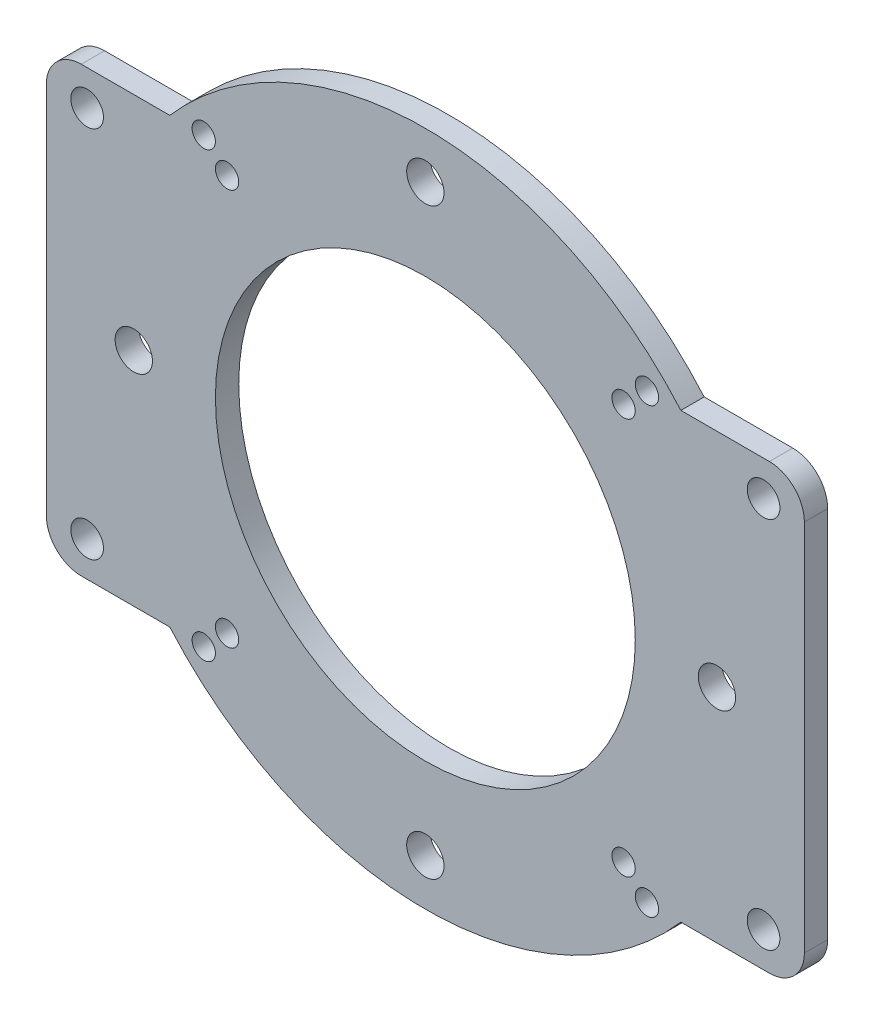
SolidWorks part; units mm, degrees
ref_plane "Front Plane" through (0, 0, 0) normal (0, 0, 1) x (1, 0, 0)
ref_plane "Top Plane" through (0, 0, 0) normal (0, 1, 0) x (1, 0, 0)
ref_plane "Right Plane" through (0, 0, 0) normal (1, 0, 0) x (0, 0, -1)
sketch "Sketch1" plane through (0, 0, 0) normal (0, 0, 1) x (1, 0, 0)
  line L0 (-32.5, 19) -> (-21.9089, 19)
  line L1 (32.5, 19) -> (32.5, -19)
  line L2 (32.5, -19) -> (21.9089, -19)
  line L3 (-32.5, -19) -> (-32.5, 19)
  line L4 (0, 39) -> (0, -40.7055) construction
  line L5 (-43.0364, 0) -> (51.1093, 0) construction
  line L6 (21.9089, 19) -> (32.5, 19)
  line L7 (-21.9089, -19) -> (-32.5, -19)
  arc A0 (-21.9089, -19) -> (21.9089, -19) centre (0, 0) ccw
  arc A1 (21.9089, 19) -> (-21.9089, 19) centre (0, 0) ccw
  circle A2 centre (0, 0) radius 18
  point P12 (27.2045, 19)
  dimension "D1" = 58
  dimension "D4" = 36
  dimension "D2" = 65
  dimension "D3" = 38
extrude "Boss-Extrude1" add sketch "Sketch1" along normal blind 2
sketch "Sketch2" plane through (0, 0, 2) normal (0, 0, 1) x (1, 0, 0)
  line L0 (-33.5817, 0) -> (33.9726, 0) construction
  line L1 (0, 32.4479) -> (0, -34.6372) construction
  circle A0 centre (-29, 16) radius 1.4
  circle A1 centre (-29, -16) radius 1.4
  circle A2 centre (29, -16) radius 1.4
  circle A3 centre (29, 16) radius 1.4
  dimension "D1" = 2.8
  dimension "D2" = 58
  dimension "D3" = 32
extrude "Cut-Extrude1" cut sketch "Sketch2" against normal blind 2
sketch "Sketch3" plane through (0, 0, 2) normal (0, 0, 1) x (1, 0, 0)
  line L0 (0, 15.6309) -> (0, -13.6849) construction
  line L1 (-12.5553, 0) -> (11.836, 0) construction
  point P5 (-17, 17)
  point P6 (17, 17)
  point P7 (17, -17)
  point P8 (-17, -17)
  point P9 (19, 19)
  point P10 (19, -19)
  point P11 (-19, -19)
  point P12 (0, 0)
  point P13 (-19, 19)
  point P14 (19, 19.7089)
  point P15 (0, 0)
  point P16 (0, 0)
  point P17 (0, 0)
  dimension "D1" = 34
  dimension "D2" = 34
  dimension "D3" = 38
  dimension "D4" = 38
hole_wizard "Ø2.0mm Dowel Hole1" positions "3DSketch1" profile "Sketch4" hole size "Ø2.0" standard "ANSI Metric" end condition through all
sketch3d "3DSketch1"
  point P0 (-19, 19, 2)
  point P3 (-17, 17, 2)
  point P6 (17, 17, 2)
  point P9 (19, 19, 2)
  point P12 (17, -17, 2)
  point P15 (19, -19, 2)
  point P18 (-19, -19, 2)
  point P21 (-17, -17, 2)
sketch "Sketch4" plane through (-19, 19, 2) normal (1, 0, 0) x (0, -1, 0)
  line L0 (0, 0) -> (0, 2)
  line L1 (0, 2) -> (1, 2)
  line L2 (1, 2) -> (1, 0)
  line L5 (1, 0) -> (0, 0)
  line L11 (0, -6.35) -> (0, 107.95) construction
  dimension "Thru Hole Dia." = 2
  dimension "Thru Hole Depth" = 2
sketch "Sketch5" plane through (0, 0, 0) normal (0, 0, 1) x (1, 0, 0)
  line L2 (0, 0) -> (14.1533, 0) construction
  line L3 (0, 0) -> (0, 14.1167) construction
  line L4 (0, 15.6309) -> (0, -13.6849) construction
  circle A0 centre (0, 25) radius 1.6
  circle A1 centre (-25, 0) radius 1.6
  circle A2 centre (25, 0) radius 1.6
  circle A3 centre (0, -25) radius 1.6
  point P8 (0, 0)
  point P13 (0, 0)
  dimension "D1" = 3.2
  dimension "D2" = 50
  dimension "D3" = 50
extrude "Cut-Extrude4" cut sketch "Sketch5" along normal through all
fillet "Fillet1" radius 3 4 edges at (-32.5, -19, 1) (-32.5, 19, 1) (32.5, 19, 1) (32.5, -19, 1)
